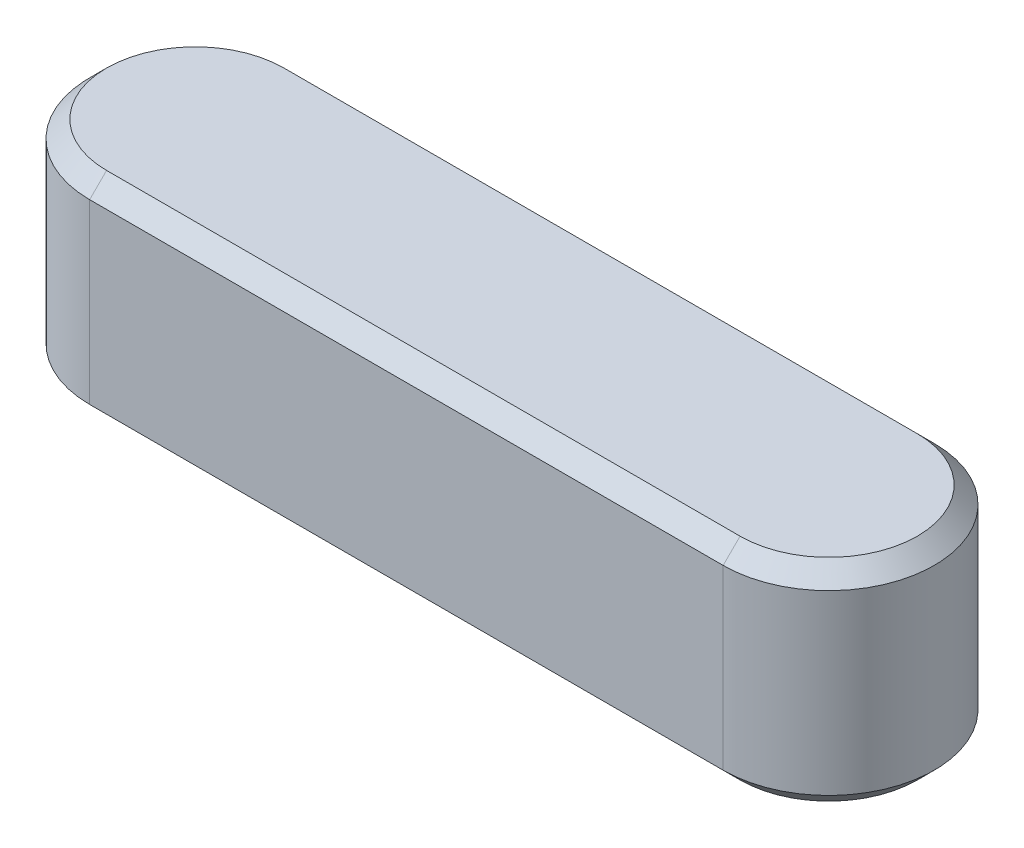
SolidWorks part; units mm, degrees
ref_plane "Front Plane" through (0, 0, 0) normal (0, 0, 1) x (1, 0, 0)
ref_plane "Top Plane" through (0, 0, 0) normal (0, 1, 0) x (1, 0, 0)
ref_plane "Right Plane" through (0, 0, 0) normal (1, 0, 0) x (0, 0, -1)
sketch "BasicSke" plane through (0, 0, 0) normal (0, 1, 0) x (1, 0, 0)
  line L0 (0, 0) -> (2, 0) construction
  line L1 (0, 1) -> (0, -1)
  line L2 (0, 1) -> (8, 1)
  line L3 (8, 1) -> (8, -1)
  line L4 (8, -1) -> (0, -1)
  line L5 (4, 1) -> (4, 0.84) construction
  circle A0 centre (1, 0) radius 1
  circle A1 centre (7, 0) radius 1
sketch "BodySke" plane through (0, 0, 0) normal (0, 1, 0) x (1, 0, 0)
  line L2 (8, 1) -> (8, -1) construction
  line L3 (8, -1) -> (0, -1) construction
  line L6 (0, 1) -> (0, -1) construction
  line L7 (0, 1) -> (8, 1) construction
  line L8 (8, 1) -> (8, -1)
  line L9 (8, -1) -> (0, -1)
  line L10 (0, 1) -> (0, -1)
  line L11 (0, 1) -> (8, 1)
extrude "BaseBody" add sketch "BodySke" along normal blind 2
chamfer "Chamfer3" [suppressed] distance 0.16 angle 45
fillet "Fillet1" 2 edges at (0, 1, 1) (0, 1, -1) type full round first side face at (4, 1, 1) second side face at (4, 1, -1) middle face at (0, 1, 0)
chamfer "Chamfer4" [suppressed] distance 0.16 angle 45
fillet "Fillet2" 2 edges at (8, 1, 1) (8, 1, -1) type full round first side face at (4.5, 1, 1) second side face at (4.5, 1, -1) middle face at (8, 1, 0)
chamfer "Chamfer5" distance 0.16 angle 45 8 edges at (4, 0, -1) (8, 0, 0) (0, 0, 0) (4, 0, 1) (0, 2, 0) (4, 2, 1) (8, 2, 0) (4, 2, -1)
equation "\"Height@BaseBody\" = \"Key_Height@BasicSke\""
equation "\"D1@Chamfer3\" = \"Chamfer@BasicSke\""
equation "\"D1@Chamfer4\" = \"Chamfer@BasicSke\""
equation "\"D1@Chamfer5\" = \"Chamfer@BasicSke\""
